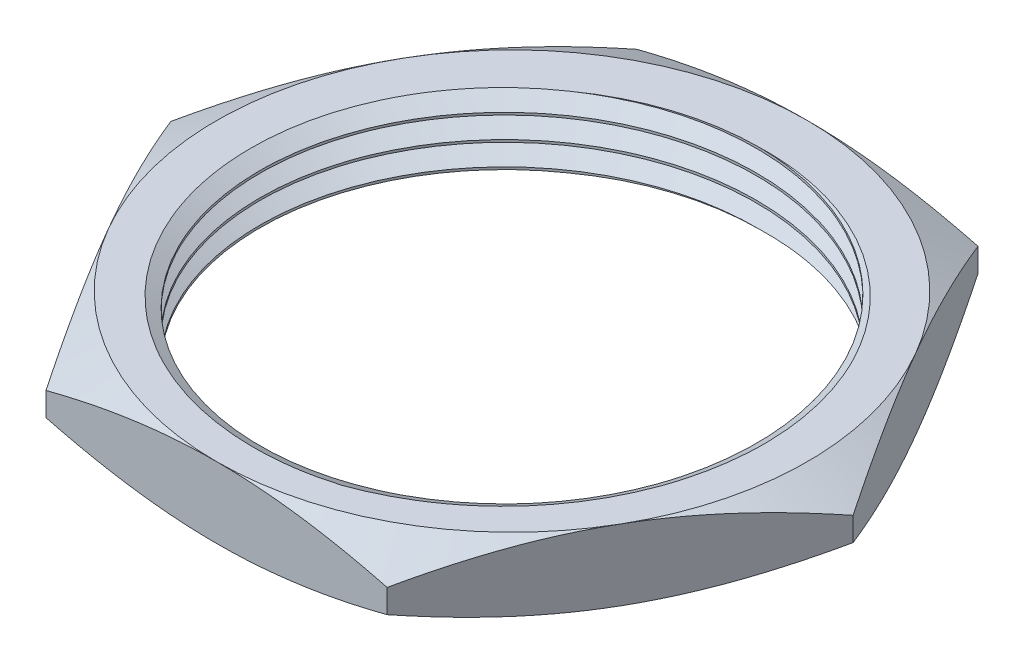
SolidWorks part; units mm, degrees
ref_plane "前视基准面" through (0, 0, 0) normal (0, 0, 1) x (1, 0, 0)
ref_plane "上视基准面" through (0, 0, 0) normal (0, 1, 0) x (1, 0, 0)
ref_plane "右视基准面" through (0, 0, 0) normal (1, 0, 0) x (0, 0, -1)
sketch "草图1" plane through (0, 0, 0) normal (0, 1, 0) x (1, 0, 0)
  line L2 (7.2169, -12.5) -> (14.4338, 0)
  line L3 (14.4338, 0) -> (7.2169, 12.5)
  line L4 (7.2169, 12.5) -> (-7.2169, 12.5)
  line L5 (-7.2169, 12.5) -> (-14.4338, 0)
  line L6 (-14.4338, 0) -> (-7.2169, -12.5)
  line L7 (-7.2169, -12.5) -> (7.2169, -12.5)
  circle A0 centre (0, 0) radius 12.5 construction
  circle A1 centre (0, 0) radius 10.5
  dimension "D1" = 25
  dimension "D2" = 21
extrude "凸台-拉伸1" add sketch "草图1" along normal blind 3
sketch "草图2" plane through (0, 0, 0) normal (0, -1, 0) x (1, 0, 0)
  circle A0 centre (0, 0) radius 10.5
  dimension "D1" = 21
curve "螺旋线/涡状线1" pitch 1 height 3 radius 10.5 centre (0, 0, 0) axis (0, 1, 0) start towards (0, 0, -1)
sketch "草图8" plane through (0, 0, 0) normal (1, 0, 0) x (0, 0, -1)
  line L0 (10.5, 0) -> (10.5, 0.9)
  line L1 (10.5, 0) -> (10.5, 3) construction
  line L2 (10.5, 0.9) -> (11.2794, 0.45)
  line L3 (11.2794, 0.45) -> (10.5, 0)
  dimension "D1" = 0.9
  dimension "D2" = 60
  dimension "D3" = 120
sweep "切除-扫描1" cut profiles "草图8" path "螺旋线/涡状线1" align with end faces yes
sketch "草图9" plane through (0, 0, 0) normal (1, 0, 0) x (0, 0, -1)
  line L0 (0, -1.962) -> (0, 2.7298) construction
  line L1 (14.4338, 2) -> (12.5, 3)
  line L2 (14.4338, 2) -> (14.4338, 3)
  line L3 (1.3605, 1.5) -> (-1.6853, 1.5) construction
  line L4 (14.4338, 1) -> (14.4338, 0)
  line L5 (14.4338, 0) -> (12.5, 0)
  line L6 (14.4338, 3) -> (12.5, 3)
  line L12 (14.4338, 1) -> (12.5, 0)
  dimension "D1" = 1.5
revolve "切除-旋转5" cut sketch "草图9" angle 360 about L0
